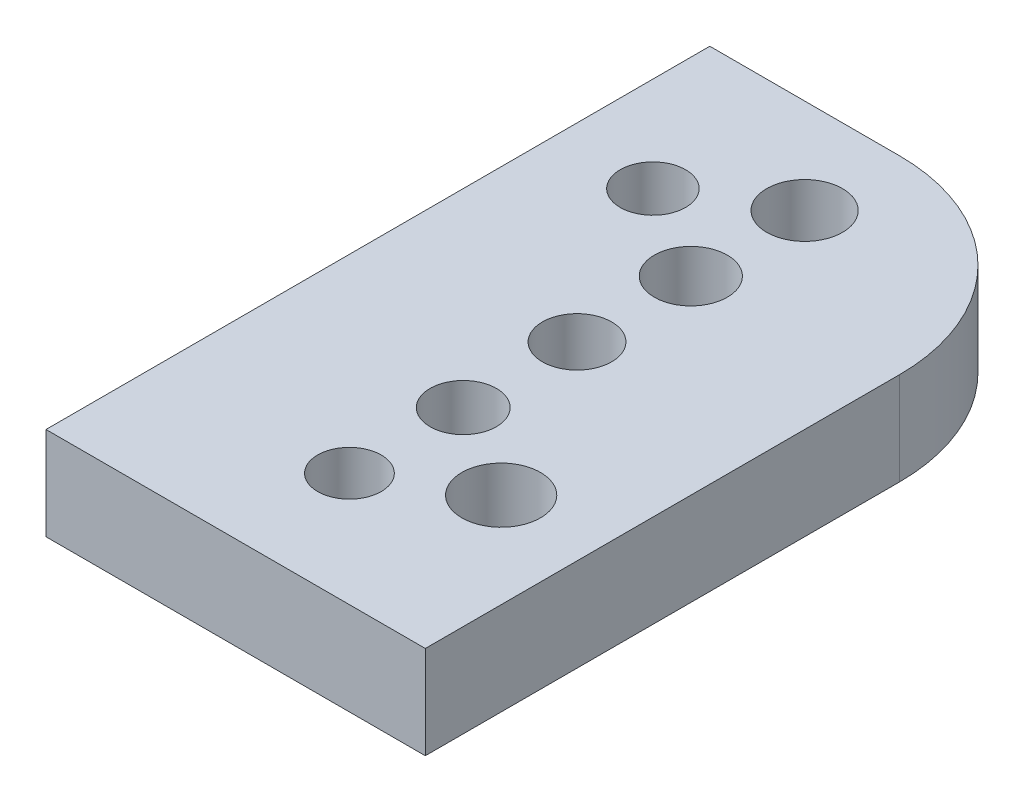
SolidWorks part; units mm, degrees
ref_plane "Plan de face" through (0, 0, 0) normal (0, 0, 1) x (1, 0, 0)
ref_plane "Plan de dessus" through (0, 0, 0) normal (0, 1, 0) x (1, 0, 0)
ref_plane "Plan de droite" through (0, 0, 0) normal (1, 0, 0) x (0, 0, -1)
sketch "Esquisse1" plane through (0, 0, 0) normal (0, 1, 0) x (1, 0, 0)
  line L1 (-10, 17.5) -> (10, 17.5)
  line L2 (-10, 17.5) -> (-10, -17.5)
  line L3 (-10, -17.5) -> (10, -17.5)
  line L4 (10, 17.5) -> (10, -17.5)
  line L5 (-10, 17.5) -> (10, -17.5) construction
  line L6 (-10, -17.5) -> (10, 17.5) construction
  point P0 (0, 0)
  dimension "D1" = 35
  dimension "D2" = 20
extrude "Boss.-Extru.1" add sketch "Esquisse1" along normal blind 4.9
sketch "Esquisse2" plane through (0, 4.9, 0) normal (0, 1, 0) x (1, 0, 0)
  line L0 (-10, -17.5) -> (10, -17.5) construction
  circle A0 centre (0, -11.5) radius 1.675
  circle A1 centre (0, -5.5) radius 1.75
  circle A2 centre (0, 0.5) radius 1.825
  circle A3 centre (0, 6.5) radius 1.925
  circle A4 centre (0, 12.5) radius 2
  circle A5 centre (5, -8.5) radius 2.075
  circle A6 centre (-5, 9.5) radius 1.725
  dimension "D1" = 3.35
  dimension "D2" = 3.5
  dimension "D3" = 3.65
  dimension "D4" = 3.85
  dimension "D9" = 4
  dimension "D11" = 4.15
  dimension "D14" = 3.45
  dimension "D5" = 6
  dimension "D6" = 6
  dimension "D7" = 6
  dimension "D8" = 6
  dimension "D10" = 6
  dimension "D12" = 5
  dimension "D13" = 3
  dimension "D15" = 3
  dimension "D16" = 5
extrude "Enlèv. mat.-Extru.1" cut sketch "Esquisse2" against normal up to next
fillet "Congé1" radius 10 1 edges at (10, 2.45, -17.5)
